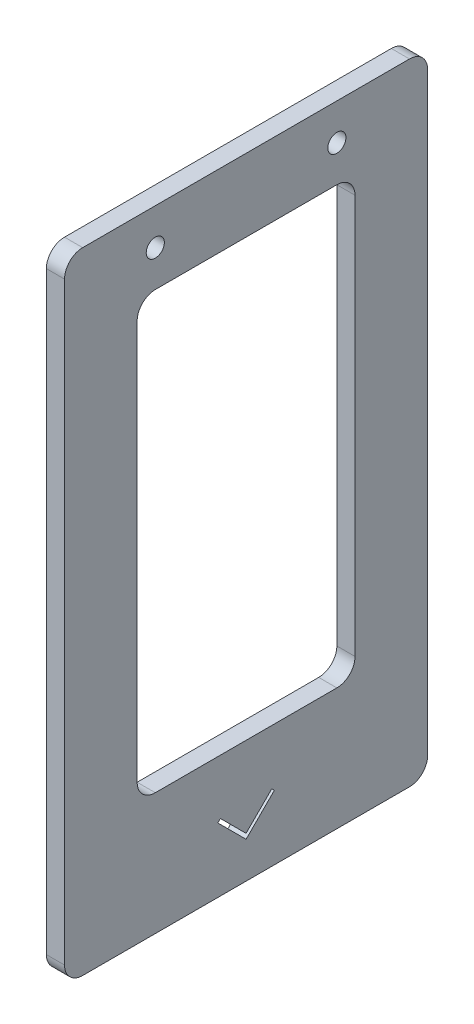
SolidWorks part; units mm, degrees
material "Balsa"
ref_plane "Front Plane" through (0, 0, 0) normal (0, 0, 1) x (1, 0, 0)
ref_plane "Top Plane" through (0, 0, 0) normal (0, 1, 0) x (1, 0, 0)
ref_plane "Right Plane" through (0, 0, 0) normal (1, 0, 0) x (0, 0, -1)
sketch "Sketch3" plane through (0, 0, 0) normal (1, 0, 0) x (0, 0, -1)
  line L0 (-31.75, -67.564) -> (31.75, -67.564)
  line L1 (-57.15, -110.236) -> (57.15, -110.236)
  line L2 (-63.5, -103.886) -> (-63.5, 103.886)
  line L3 (-57.15, 110.236) -> (57.15, 110.236)
  line L4 (63.5, -103.886) -> (63.5, 103.886)
  line L5 (-63.5, -110.236) -> (63.5, 110.236) construction
  line L6 (-63.5, 110.236) -> (63.5, -110.236) construction
  line L8 (-38.1, -61.214) -> (-38.1, 78.486)
  line L9 (-31.75, 84.836) -> (31.75, 84.836)
  line L11 (0, 0) -> (38.1, 84.836) construction
  line L12 (-38.1, 84.836) -> (0, 0) construction
  line L13 (38.1, -61.214) -> (38.1, 78.486)
  arc A0 (-57.15, -110.236) -> (-63.5, -103.886) centre (-57.15, -103.886) cw
  arc A1 (63.5, -103.886) -> (57.15, -110.236) centre (57.15, -103.886) cw
  arc A2 (63.5, 103.886) -> (57.15, 110.236) centre (57.15, 103.886) ccw
  arc A3 (-63.5, 103.886) -> (-57.15, 110.236) centre (-57.15, 103.886) cw
  arc A4 (31.75, -67.564) -> (38.1, -61.214) centre (31.75, -61.214) ccw
  arc A5 (-31.75, -67.564) -> (-38.1, -61.214) centre (-31.75, -61.214) cw
  arc A6 (31.75, 84.836) -> (38.1, 78.486) centre (31.75, 78.486) cw
  arc A7 (-38.1, 78.486) -> (-31.75, 84.836) centre (-31.75, 78.486) cw
  point P0 (0, 0)
  point P6 (0, 0)
  point P26 (38.1, -67.564)
  dimension "D7" = 6.35
  dimension "D8" = 6.35
  dimension "D1" = 220.472
  dimension "D2" = 127
  dimension "D3" = 76.2
  dimension "D4" = 152.4
  dimension "D5" = 25.4
  dimension "D6" = 25.4
extrude "Boss-Extrude2" add sketch "Sketch3" along normal blind 6.35
sketch "Sketch4" plane through (6.35, 0, 0) normal (1, 0, 0) x (0, 0, -1)
  line L0 (-57.15, -110.236) -> (57.15, -110.236) construction
  line L5 (0, -95.7399) -> (-8.9803, -86.7597)
  line L6 (-8.9803, -86.7597) -> (-9.8783, -87.6577)
  line L8 (-9.8783, -87.6577) -> (0, -97.536)
  line L9 (0, -97.536) -> (9.8783, -87.6577)
  line L10 (9.8783, -87.6577) -> (8.9803, -86.7597)
  line L11 (8.9803, -86.7597) -> (0, -95.7399)
  line L12 (0, 3.4925) -> (0, -3.4925) construction
  dimension "D1" = 12.7
  dimension "D2" = 12.7
  dimension "D3" = 1.27
extrude "Cut-Extrude1" cut sketch "Sketch4" against normal up to next
sketch "Sketch5" plane through (6.35, 0, 0) normal (1, 0, 0) x (0, 0, -1)
  line L0 (-31.75, 97.536) -> (31.75, 97.536) construction
  line L1 (31.75, 97.536) -> (63.5, 97.536) construction
  line L2 (63.5, -103.886) -> (63.5, 103.886) construction
  line L3 (-31.75, 97.536) -> (-63.5, 97.536) construction
  line L4 (-63.5, 103.886) -> (-63.5, -103.886) construction
  line L5 (57.15, 110.236) -> (-57.15, 110.236) construction
  circle A0 centre (-31.75, 97.536) radius 3.175
  circle A1 centre (31.75, 97.536) radius 3.175
  dimension "D1" = 6.35
  dimension "D2" = 63.5
  dimension "D3" = 12.7
extrude "Cut-Extrude2" cut sketch "Sketch5" against normal through all both and the other way through all
